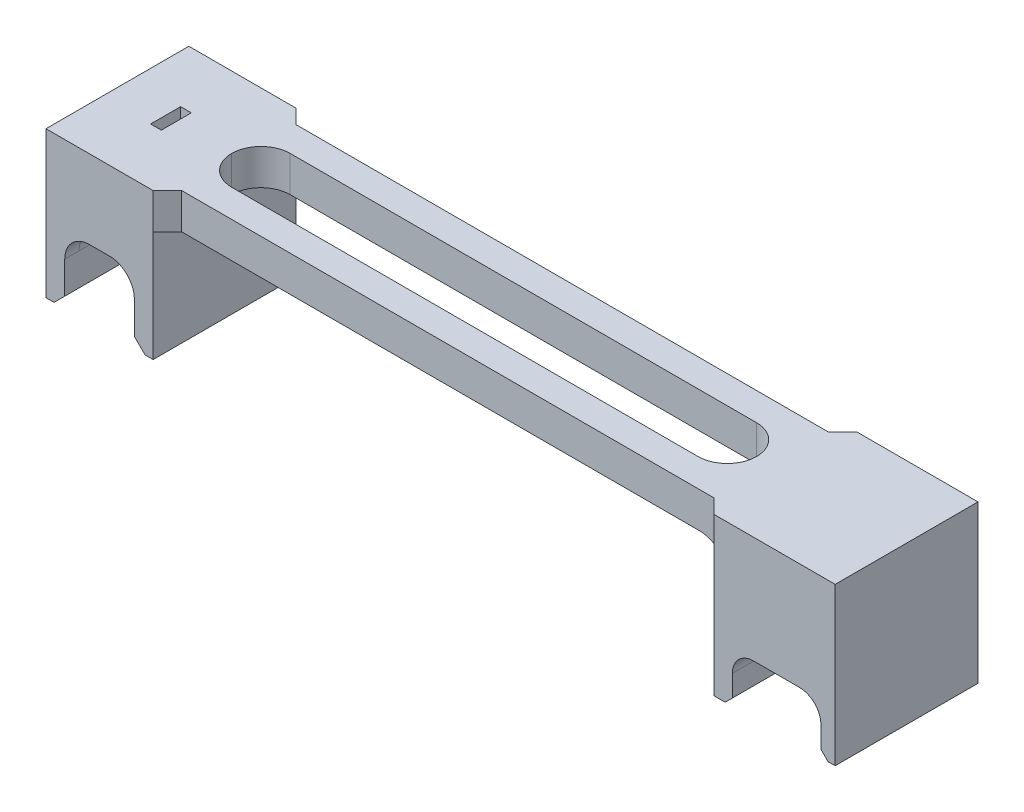
SolidWorks part; units mm, degrees
ref_plane "정면" through (0, 0, 0) normal (0, 0, 1) x (1, 0, 0)
ref_plane "윗면" through (0, 0, 0) normal (0, 1, 0) x (1, 0, 0)
ref_plane "우측면" through (0, 0, 0) normal (1, 0, 0) x (0, 0, -1)
sketch "스케치1" plane through (0, 0, 0) normal (0, 0, 1) x (1, 0, 0)
  line L0 (-96, 0) -> (0, 0)
  line L1 (0, 0) -> (0, -21.5)
  line L2 (0, -21.5) -> (7.6, -21.5)
  line L3 (7.6, -21.5) -> (7.6, 5)
  line L4 (7.6, 5) -> (-96, 5)
  line L5 (-96, 5) -> (-96, 0)
  dimension "D1" = 5
  dimension "D2" = 96
  dimension "D3" = 7.6
  dimension "D4" = 21.5
extrude "보스-돌출1" add sketch "스케치1" along normal blind 16
sketch "스케치4" plane through (0, 0, 0) normal (0, -1, 0) x (1, 0, 0)
  line L0 (-96, 8) -> (-7.1358, 8) construction
  line L1 (-96, 16) -> (-96, 0) construction
  line L2 (0, 16) -> (0, 0) construction
  line L3 (-91.75, 5.9) -> (-90.25, 5.9)
  line L4 (-91.75, 5.9) -> (-91.75, 10.1)
  line L5 (-91.75, 10.1) -> (-90.25, 10.1)
  line L6 (-90.25, 5.9) -> (-90.25, 10.1)
  line L7 (-91.75, 5.9) -> (-90.25, 10.1) construction
  line L8 (-91.75, 10.1) -> (-90.25, 5.9) construction
  line L9 (-9, 3.9) -> (-82.5, 3.9)
  line L10 (-9, 3.9) -> (-9, 12.1)
  line L11 (-9, 12.1) -> (-82.5, 12.1)
  line L12 (-82.5, 3.9) -> (-82.5, 12.1)
  line L13 (-9, 3.9) -> (-82.5, 12.1) construction
  line L14 (-9, 12.1) -> (-82.5, 3.9) construction
  point P4 (-91, 8)
  point P9 (-45.75, 8)
  dimension "D1" = 1.5
  dimension "D2" = 4.25
  dimension "D3" = 7.75
  dimension "D4" = 9
  dimension "D5" = 8.2
  dimension "D6" = 4.2
extrude "컷-돌출1" cut sketch "스케치4" against normal blind 10
fillet "필렛1" radius 4.1 4 edges at (-82.5, 2.5, 3.9) (-82.5, 2.5, 12.1) (-9, 2.5, 3.9) (-9, 2.5, 12.1)
sketch "스케치6" plane through (0, 5, 0) normal (0, 1, 0) x (1, 0, 0)
  line L0 (7.6, -16) -> (-96, -16) construction
  line L1 (-96, 0) -> (-86, 0)
  line L2 (-96, 0) -> (-96, -16)
  line L3 (-96, -16) -> (-86, -16)
  line L4 (-86, 0) -> (-86, -16)
  line L6 (-90.25, -5.9) -> (-90.25, -10.1) construction
  line M5 (-91.75, -5.9) -> (-90.25, -5.9)
  line M6 (-90.25, -5.9) -> (-90.25, -10.1)
  line M7 (-90.25, -10.1) -> (-91.75, -10.1)
  line M8 (-91.75, -10.1) -> (-91.75, -5.9)
  line M15 (7.6, 0) -> (-96, 0)
  line M16 (-96, 0) -> (-96, -16)
  line M17 (-96, -16) -> (7.6, -16)
  dimension "D1" = 4.25
extrude "보스-돌출4" add sketch "스케치6" against normal blind 11 contours L4 M15 M16 M17 M8 M5 M6 M7 region at (-91, 5, 0.1887)
sketch "스케치10" plane through (0, -6, 0) normal (0, -1, 0) x (1, 0, 0)
  line L0 (-91, 10.1) -> (-91, 5.9) construction
  line L1 (-90.25, 10.1) -> (-91.75, 10.1) construction
  line L2 (-91.75, 5.9) -> (-90.25, 5.9) construction
  line L3 (-91.75, 8) -> (-90.25, 8) construction
  line L4 (-91.75, 10.1) -> (-91.75, 5.9) construction
  line L5 (-90.25, 5.9) -> (-90.25, 10.1) construction
  line L7 (-95.875, 0) -> (-86.125, 0)
  line L8 (-95.875, 0) -> (-95.875, 16)
  line L9 (-95.875, 16) -> (-86.125, 16)
  line L10 (-86.125, 0) -> (-86.125, 16)
  line L11 (-95.875, 0) -> (-86.125, 16) construction
  line L12 (-95.875, 16) -> (-86.125, 0) construction
  line L13 (-98.5, 0) -> (-83.5, 0)
  line L14 (-98.5, 0) -> (-98.5, 16)
  line L15 (-98.5, 16) -> (-83.5, 16)
  line L16 (-83.5, 0) -> (-83.5, 16)
  line L17 (-98.5, 0) -> (-83.5, 16) construction
  line L18 (-98.5, 16) -> (-83.5, 0) construction
  point P12 (-91, 8)
  point P17 (-91, 8)
  line M6 (-86, 0) -> (-86, 16)
  line M7 (-86, 16) -> (-96, 16)
  line M8 (-96, 16) -> (-96, 0)
  line M9 (-96, 0) -> (-86, 0)
  dimension "D1" = 9.75
  dimension "D2" = 15
extrude "보스-돌출6" add sketch "스케치10" along normal blind 13 and the other way up to vertex (11 mm away) contours L8 M9 M7 M8 | L15 L14 L13 M8 | L10 M9 M6 M7 | L13 L16 L15 M6 region at (-95.9375, -6, 8) region at (-86.0625, -6, 8) region at (-97.25, -6, 8) region at (-84.75, -6, 8) other way up to point (7.6, 5, 16)
fillet "필렛2" radius 3.5 2 edges at (-86.125, -6, 8) (-95.875, -6, 8)
sketch "스케치11" plane through (0, 0, 16) normal (0, 0, 1) x (1, 0, 0)
  line L0 (-98.5, 5) -> (-98.5, -19)
  line L1 (-98.5, -19) -> (-95.875, -19)
  line L2 (-92.375, -6) -> (-83.5, -6) construction
  line L3 (-83.5, -19) -> (-83.5, 0) construction
  line L4 (-83.5, -6) -> (-98.5, -6) construction
  line L5 (-95.875, -19) -> (-95.875, -6)
  line L6 (-86.125, -19) -> (-86.125, -6)
  line L7 (-86.125, -6) -> (-95.875, -6)
  line L8 (-86.125, -19) -> (-83.5, -19)
  line L9 (-83.5, -19) -> (-83.5, 5)
  line L10 (7.6, 5) -> (-98.5, 5) construction
  line L11 (-83.5, 5) -> (-98.5, 5)
extrude "보스-돌출7" add sketch "스케치11" along normal blind 2
sketch "스케치12" plane through (0, 0, 0) normal (0, 0, -1) x (-1, 0, 0)
  line L0 (89.625, -6) -> (98.5, -6) construction
  line L1 (98.5, 5) -> (98.5, -19) construction
  line L2 (98.5, -6) -> (83.5, -6) construction
  line L3 (83.5, -19) -> (83.5, 0) construction
  line L4 (83.5, 5) -> (83.5, -19)
  line L5 (-7.6, 5) -> (98.5, 5) construction
  line L6 (83.5, -19) -> (86.125, -19)
  line L7 (86.125, -19) -> (86.125, -6)
  line L8 (83.5, 5) -> (98.5, 5)
  line L9 (98.5, 5) -> (98.5, -19)
  line L10 (98.5, -19) -> (95.875, -19)
  line L11 (95.875, -19) -> (95.875, -6)
  line L12 (95.875, -6) -> (86.125, -6)
extrude "보스-돌출8" add sketch "스케치12" along normal blind 2
fillet "필렛4" radius 3.5 4 edges at (-95.875, -6, -1) (-86.125, -6, -1) (-86.125, -6, 17) (-95.875, -6, 17)
sketch "스케치13" plane through (-98.5, 0, 0) normal (-1, 0, 0) x (0, 0, 1)
  line L0 (18, 5) -> (18, -19) construction
  line L1 (-2, -19) -> (18, -19)
  line L2 (-2, -19) -> (-2, -15.5)
  line L3 (-2, -15.5) -> (18, -15.5)
  line L4 (18, -19) -> (18, -15.5)
  dimension "D1" = 3.5
extrude "컷-돌출2" cut sketch "스케치13" against normal up to vertex (15 mm away) up to point (-83.5, -19, -2)
chamfer "모따기1" distance 2 2 edges at (-83.5, 2.5, 16) (-83.5, 2.5, 0)
chamfer "모따기2" distance 1.5 angle 45 2 edges at (-95.875, -15.5, 8) (-86.125, -15.5, 8)
sketch "스케치14" plane through (0, 0, 0) normal (0, -1, 0) x (1, 0, 0)
  line L1 (-81.5, 0) -> (0, 0) construction
  line L2 (0, 16) -> (-5, 16)
  line L3 (0, 16) -> (0, 0)
  line L4 (0, 0) -> (-5, 0)
  line L5 (-5, 16) -> (-5, 0)
  dimension "D1" = 5
extrude "보스-돌출9" add sketch "스케치14" along normal blind 13
sketch "스케치15" plane through (0, -13, 0) normal (0, -1, 0) x (1, 0, 0)
  line L7 (-5, 0) -> (0, 0) construction
  line L8 (-5, 16) -> (-2.4, 16)
  line L9 (-5, 16) -> (-5, 0)
  line L10 (-5, 0) -> (-2.4, 0)
  line L11 (-2.4, 16) -> (-2.4, 0)
  line L12 (0, 0) -> (0, 16) construction
  dimension "D1" = 2.4
extrude "보스-돌출10" add sketch "스케치15" along normal blind 4
sketch "스케치18" plane through (0, 0, 16) normal (0, 0, 1) x (1, 0, 0)
  line L0 (-5, -17) -> (-5, 5)
  line L1 (7.6, 5) -> (-81.5, 5) construction
  line L2 (-5, 5) -> (7.6, 5)
  line L3 (7.6, 5) -> (7.6, -21.5)
  line L4 (7.6, -21.5) -> (0, -21.5)
  line L5 (0, -21.5) -> (0, -13)
  line L6 (0, -13) -> (-2.4, -13)
  line L7 (-2.4, -13) -> (-2.4, -17)
  line L8 (-2.4, -17) -> (-5, -17)
extrude "보스-돌출11" add sketch "스케치18" along normal blind 2 and the other way blind 18
chamfer "모따기4" distance 2 angle 45 2 edges at (-5, 2.5, 0) (-5, 2.5, 16)
sketch "스케치19" plane through (0, -21.5, 0) normal (0, -1, 0) x (1, 0, 0)
  line L1 (0, 18) -> (12, 18)
  line L2 (0, 18) -> (0, -2)
  line L3 (0, -2) -> (12, -2)
  line L4 (12, 18) -> (12, -2)
  dimension "D1" = 12
extrude "보스-돌출12" add sketch "스케치19" against normal blind 26.5
sketch "스케치20" plane through (0, -21.5, 0) normal (0, -1, 0) x (1, 0, 0)
  line L0 (0, 18) -> (12, 18) construction
  line L1 (10, 18) -> (0, 18)
  line L2 (10, 18) -> (10, -2)
  line L3 (10, -2) -> (0, -2)
  line L4 (0, 18) -> (0, -2)
  dimension "D1" = 10
extrude "컷-돌출3" cut sketch "스케치20" against normal blind 8.5
fillet "필렛6" radius 4 1 edges at (-5, 0, 8)
sketch "스케치21" plane through (0, -13, 0) normal (0, -1, 0) x (1, 0, 0)
  line L1 (10, 18) -> (-2.4, 18)
  line L2 (10, 18) -> (10, -2)
  line L3 (10, -2) -> (-2.4, -2)
  line L4 (-2.4, 18) -> (-2.4, -2)
extrude "컷-돌출4" cut sketch "스케치21" against normal blind 3
fillet "필렛7" radius 3 2 edges at (10, -10, 8) (-2.4, -10, 8)
sketch "스케치22" plane through (10, 0, 0) normal (-1, 0, 0) x (0, 0, 1)
  line L1 (-2, -21.5) -> (18, -21.5)
  line L2 (-2, -21.5) -> (-2, -17)
  line L3 (-2, -17) -> (18, -17)
  line L4 (18, -21.5) -> (18, -17)
extrude "컷-돌출5" cut sketch "스케치22" against normal blind 3
chamfer "모따기5" distance 1 angle 45 2 edges at (-2.4, -17, 8) (10, -17, 8)
